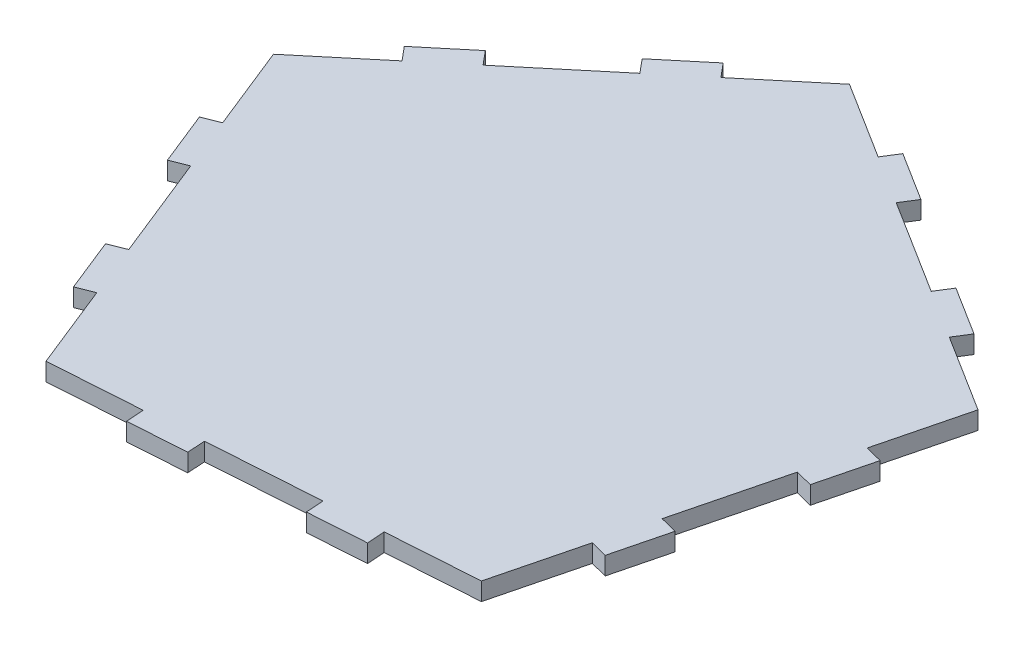
SolidWorks part; units mm, degrees
ref_plane "Front Plane" through (0, 0, 0) normal (0, 0, 1) x (1, 0, 0)
ref_plane "Top Plane" through (0, 0, 0) normal (0, 1, 0) x (1, 0, 0)
ref_plane "Right Plane" through (0, 0, 0) normal (1, 0, 0) x (0, 0, -1)
sketch "Sketch1" plane through (0, 0, 0) normal (0, 1, 0) x (1, 0, 0)
  line L1 (-59.9258, 15.1181) -> (-32.8962, -52.3211)
  line L2 (-32.8962, -52.3211) -> (39.5948, -47.4543)
  line L3 (39.5948, -47.4543) -> (57.3672, 22.9927)
  line L4 (57.3672, 22.9927) -> (-4.14, 61.6646)
  line L5 (-4.14, 61.6646) -> (-59.9258, 15.1181)
  circle A0 centre (0, 0) radius 50 construction
  dimension "D1" = 100
extrude "Boss-Extrude1" add sketch "Sketch1" along normal blind 3.18
ref_axis "Axis" through (0, 3.339, 0) along (0, -1, 0)
sketch "Axis Check" plane through (0, 3.18, 0) normal (0, 1, 0) x (1, 0, 0)
  line L0 (3.3493, -49.8877) -> (-4.14, 61.6646) construction
  line L1 (-32.8962, -52.3211) -> (39.5948, -47.4543) construction
  line L2 (57.3672, 22.9927) -> (-46.411, -18.6015) construction
  line L3 (-59.9258, 15.1181) -> (-32.8962, -52.3211) construction
  line L4 (-32.0329, 38.3913) -> (39.5948, -47.4543) construction
  line L5 (-4.14, 61.6646) -> (-59.9258, 15.1181) construction
  line L6 (-59.9258, 15.1181) -> (48.481, -12.2308) construction
  line L7 (39.5948, -47.4543) -> (57.3672, 22.9927) construction
  line L8 (-32.8962, -52.3211) -> (26.6136, 42.3287) construction
  line L9 (57.3672, 22.9927) -> (-4.14, 61.6646) construction
sketch "Sketch2" plane through (0, 0, 0) normal (0, -1, 0) x (1, 0, 0)
  line L0 (-53.8107, 0.1392) -> (-50.859, -1.0438)
  line L1 (-53.8107, 0.1392) -> (-50.1723, 9.2172)
  line L2 (-50.859, -1.0438) -> (-47.2205, 8.0342)
  line L3 (-50.1723, 9.2172) -> (-47.2205, 8.0342)
  line L4 (-59.9258, -15.1181) -> (-32.8962, 52.3211) construction
  line L5 (-42.6498, 27.9858) -> (-39.0113, 37.0638)
  line L6 (-42.6498, 27.9858) -> (-39.6981, 26.8028)
  line L7 (-39.0113, 37.0638) -> (-36.0596, 35.8808)
  line L8 (-39.6981, 26.8028) -> (-36.0596, 35.8808)
  line L9 (-46.411, 18.6015) -> (-19.2439, 7.7129) construction
  line L10 (-40.8306, 32.5248) -> (-37.8788, 31.3418) construction
  dimension "D1" = 3.18
  dimension "D2" = 9.78
  dimension "D3" = 10.11
extrude "Cut F" [suppressed] cut sketch "Sketch2" against normal through all
sketch "Sketch4" [suppressed] plane through (0, 3.18, 0) normal (0, 1, 0) x (1, 0, 0)
  line L9 (26.6136, 42.3287) -> (-26.6136, -42.3287) construction
  line L10 (57.3672, 22.9927) -> (-4.14, 61.6646) construction
  line L11 (-27.7286, -6.3206) -> (-6.3206, 27.7286)
  line L12 (-27.7286, -6.3206) -> (6.3206, -27.7286)
  line L13 (-6.3206, 27.7286) -> (27.7286, 6.3206)
  line L14 (6.3206, -27.7286) -> (27.7286, 6.3206)
  line L15 (-27.7286, -6.3206) -> (27.7286, 6.3206) construction
  line L16 (-6.3206, 27.7286) -> (6.3206, -27.7286) construction
  line L20 (0, 0) -> (39.0006, -24.5211) construction
  circle A0 centre (-14.9622, -23.7972) radius 3.25
  circle A1 centre (23.7972, -14.9622) radius 3.25
  point P5 (0, 0)
  point P6 (-14.9622, -23.7972)
  dimension "D3" = 6.5
  dimension "D1" = 40.22
  dimension "D2" = 40.22
  dimension "D4" = 8
  dimension "D5" = 8
extrude "Top Cut" [suppressed] cut sketch "Sketch4" against normal blind 10
sketch "Sketch7" [suppressed] plane through (0, 3.18, 0) normal (0, 1, 0) x (1, 0, 0)
  line L0 (0, 0) -> (26.6136, 42.3287) construction
  line L1 (57.3672, 22.9927) -> (-4.14, 61.6646) construction
  line L2 (1.0645, 1.6931) -> (-22.7326, 16.6553) construction
  line L3 (-6.1086, 1.4782) -> (-24.8617, 13.269) construction
  line L5 (-6.3206, 27.7286) -> (-27.7286, -6.3206) construction
  circle A0 centre (-22.7326, 16.6553) radius 1
  circle A1 centre (-24.8617, 13.269) radius 1
  dimension "D5" = 2
  dimension "D1" = 4
  dimension "D2" = 2
  dimension "D3" = 8
  dimension "D4" = 8
extrude "Top Cut 2" [suppressed] cut sketch "Sketch7" against normal through all
sketch "Bottom Cut" plane through (0, 3.18, 0) normal (0, 1, 0) x (1, 0, 0)
  line L0 (3.3493, -49.8877) -> (-4.14, 61.6646) construction
  line L2 (-32.8962, -52.3211) -> (39.5948, -47.4543) construction
  line L5 (-33.7535, -23.9959) -> (-33.7535, 24.3041) construction
  circle A4 centre (-33.7535, -23.9959) radius 1.6
  circle A5 centre (-32.1535, 24.3041) radius 1.6
  circle A6 centre (18.6465, 9.0041) radius 1.6
  circle A7 centre (18.6465, -18.8959) radius 1.6
  point P13 (0, 0)
  point P14 (0, 0)
  dimension "D1" = 3.2
  dimension "D4" = 27.9
  dimension "D3" = 5.1
  dimension "D2" = 48.3
  dimension "D5" = 50.8
sketch "Sketch3" plane through (0, 3.18, 0) normal (0, 1, 0) x (1, 0, 0)
  line L0 (0, 0) -> (-40.9819, 49.1167) construction
  line L1 (-49.5112, 27.9494) -> (-45.4366, 23.066)
  line L3 (-45.4366, 23.066) -> (-37.5894, 29.6135)
  line L4 (-41.664, 34.4969) -> (-37.5894, 29.6135)
  line L5 (-4.14, 61.6646) -> (-59.9258, 15.1181) construction
  line L6 (-71.9961, 5.0469) -> (-69.9588, 2.6052)
  line L7 (-71.9961, 5.0469) -> (-47.4739, 25.5077)
  line L14 (-26.4764, 47.1691) -> (-22.4018, 42.2857)
  line L16 (-22.4018, 42.2857) -> (-14.5546, 48.8333)
  line L17 (-18.6292, 53.7166) -> (-14.5546, 48.8333)
  line L18 (-42.539, 27.5695) -> (-41.513, 26.3398) construction
  line L19 (-49.5112, 27.9494) -> (-41.664, 34.4969)
  line L21 (-26.4764, 47.1691) -> (-18.6292, 53.7166)
  line L22 (-16.5919, 51.275) -> (4.7866, 69.1127)
  line L23 (-39.6267, 32.0552) -> (-24.4391, 44.7274)
  line M18 (-4.14, 61.6646) -> (-59.9258, 15.1181)
  dimension "D1" = 3.18
  dimension "D2" = 10.22
  dimension "D3" = 9.89
  dimension "D4" = 100
extrude "Extrude M" add sketch "Sketch3" against normal up to surface (3.18 mm away) contours L21 L14 L7 L17 | L19 L1 L4 M18 region at (-44.5689, 3.18, -30.0023) region at (-21.5341, 3.18, -49.222) up to face at (0, 0, 0)
pattern_circular "Circle F" [suppressed] count 5 over 360 about axis through (0, 3.339, 0) along (0, -1, 0) of bodies 173
pattern_circular "Circle M" count 5 over 360 about axis through (0, 3.339, 0) along (0, -1, 0) of "Extrude M"
pattern_circular "Circle Side F" [suppressed] count 5 over 360 about axis through (0, 3.339, 0) along (0, -1, 0) of bodies 173
pattern_circular "Circle Side M" [suppressed] count 5 over 360 about axis through (0, 3.339, 0) along (0, -1, 0) of bodies 168
equation "\"kerf\"= .22mm"
equation "\"tabWidthF\"= 10 - \"kerf\""
equation "\"tabThickness\"= 3.18"
equation "\"D1@Sketch2\"=\"tabThickness\""
equation "\"tabWidthM\"= 10 + \"kerf\""
equation "\"halfkerf\"= \"kerf\" / 2.00mm"
equation "\"tabLength\" = \"kerf\" + 12"
